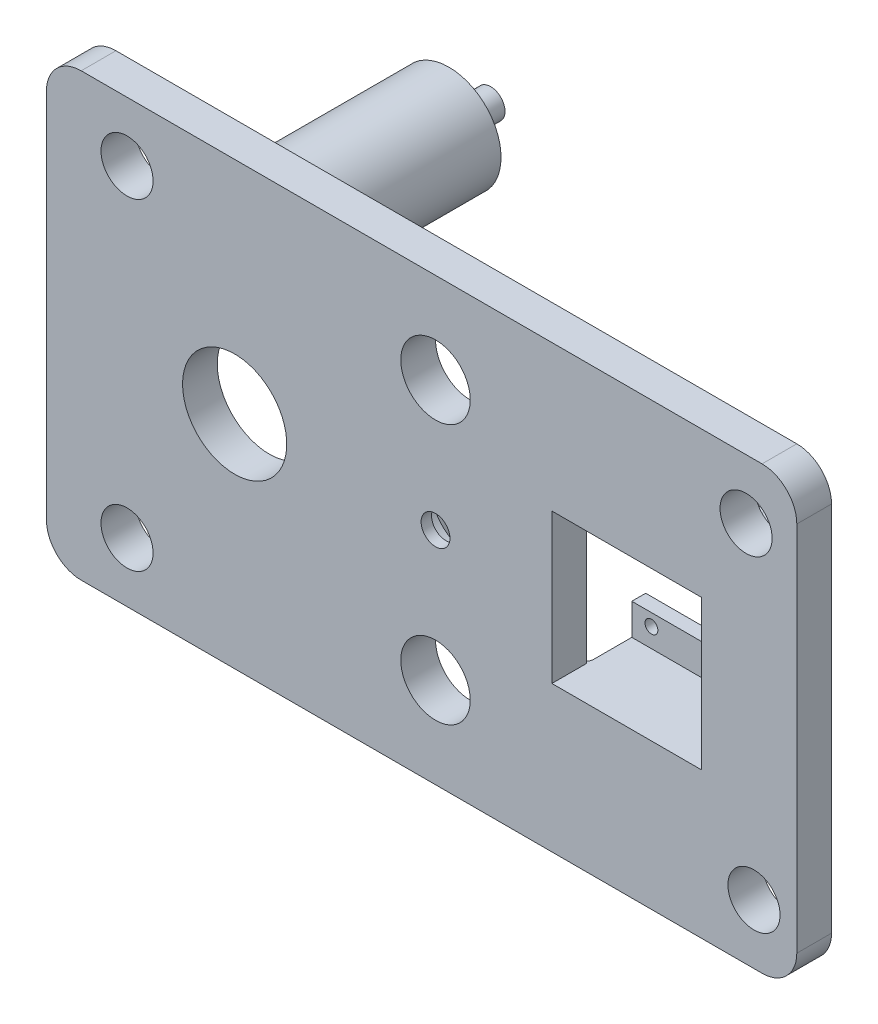
SolidWorks part; units mm, degrees
ref_plane "Front Plane" through (0, 0, 0) normal (0, 0, 1) x (1, 0, 0)
ref_plane "Top Plane" through (0, 0, 0) normal (0, 1, 0) x (1, 0, 0)
ref_plane "Right Plane" through (0, 0, 0) normal (1, 0, 0) x (0, 0, -1)
sketch "Sketch1" plane through (0, 0, 0) normal (0, 0, 1) x (1, 0, 0)
  line L1 (-108, 63.5) -> (108, 63.5)
  line L2 (-108, 63.5) -> (-108, -63.5)
  line L3 (-108, -63.5) -> (108, -63.5)
  line L4 (108, 63.5) -> (108, -63.5)
  line L5 (-108, 63.5) -> (108, -63.5) construction
  line L6 (-108, -63.5) -> (108, 63.5) construction
  point P0 (0, 0)
  dimension "D1" = 127
  dimension "D2" = 216
extrude "Boss-Extrude1" add sketch "Sketch1" along normal blind 10
fillet "Fillet1" radius 10 1 edges at (-108, 63.5, 5)
fillet "Fillet2" radius 10 3 edges at (-108, -63.5, 5) (108, 63.5, 5) (108, -63.5, 5)
sketch "Sketch9" plane through (0, 0, 0) normal (0, 0, -1) x (-1, 0, 0)
  line L0 (-98, 63.5) -> (98, 63.5) construction
  line L1 (-37.5, -21.5) -> (-80.5, -21.5)
  line L2 (-37.5, -21.5) -> (-37.5, 21.5)
  line L3 (-37.5, 21.5) -> (-80.5, 21.5)
  line L4 (-80.5, -21.5) -> (-80.5, 21.5)
  line L5 (-37.5, -21.5) -> (-80.5, 21.5) construction
  line L6 (-37.5, 21.5) -> (-80.5, -21.5) construction
  line L8 (108, 0) -> (-108, 0) construction
  line L9 (108, 53.5) -> (108, -53.5) construction
  line L10 (-108, -53.5) -> (-108, 53.5) construction
  circle A0 centre (-4, 0) radius 11.35
  point P2 (-59, 0)
  dimension "D6" = 22.7
  dimension "D1" = 27.5
  dimension "D2" = 55
  dimension "D3" = 43
  dimension "D4" = 43
  dimension "D5" = 63.5
extrude "Cut-Extrude4" cut sketch "Sketch9" against normal blind 7 contours A0
sketch "Sketch12" plane through (0, 0, 7) normal (0, 0, -1) x (-1, 0, 0)
  circle A0 centre (-4, 0) radius 4.15
  dimension "D1" = 8.3
extrude "Cut-Extrude5" cut sketch "Sketch12" against normal blind 7
extrude "Cut-Extrude6" cut sketch "Sketch9<4>" against normal through all contours L3 L4 L1 L2
sketch "Sketch9<4>" plane through (0, 0, 0) normal (0, 0, -1) x (-1, 0, 0) same geometry as "Sketch9"
sketch "Sketch13" plane through (0, 0, 0) normal (0, 0, -1) x (-1, 0, 0)
  line L1 (-37.5, -21.5) -> (-80.5, -21.5)
  line L2 (-37.5, -21.5) -> (-37.5, -25.5)
  line L3 (-37.5, -25.5) -> (-80.5, -25.5)
  line L4 (-80.5, -21.5) -> (-80.5, -25.5)
  dimension "D1" = 4
  dimension "D2" = 43
extrude "Boss-Extrude2" add sketch "Sketch13" along normal blind 17
ref_plane "Plane3" through (0, -21.5, 0) normal (0, 1, 0) x (1, 0, 0)
ref_plane "Plane4" through (0, 0, 0) normal (0, 0, -1) x (-1, 0, 0)
ref_plane "Plane6" through (80.5, 0, 0) normal (1, 0, 0) x (0, 0, -1)
sketch "Sketch16" plane through (80.5, 0, 0) normal (1, 0, 0) x (0, 0, -1)
  line L0 (17, -21.5) -> (0, -21.5) construction
  line L1 (17.0075, -21.5) -> (0.1109, -21.5)
  line L2 (17.0075, -21.5) -> (17.0075, -25.5)
  line L3 (17.0075, -25.5) -> (0.1109, -25.5)
  line L4 (0.1109, -21.5) -> (0.1109, -25.5)
  line L5 (17, -25.5) -> (0, -25.5) construction
fillet "Fillet4" radius 2 3 edges at (59, -25.5, 0) (37.5, -23.5, 0) (80.5, -23.5, 0)
sketch "Sketch17" plane through (0, -21.5, 0) normal (0, 1, 0) x (1, 0, 0)
  line L0 (80.5, 17.0075) -> (80.5, 0.1109) construction
  line L1 (37.5, 17) -> (80.5, 17)
  line L2 (37.5, 17) -> (37.5, 13)
  line L3 (37.5, 13) -> (80.5, 13)
  line L4 (80.5, 17) -> (80.5, 13)
  dimension "D1" = 4
extrude "Boss-Extrude5" add sketch "Sketch17" along normal blind 9
sketch "Sketch18" plane through (0, 0, 0) normal (0, 0, -1) x (-1, 0, 0)
  line L1 (-37.5, 21.5) -> (-80.5, 21.5)
  line L2 (-37.5, 21.5) -> (-37.5, 25.5)
  line L3 (-37.5, 25.5) -> (-80.5, 25.5)
  line L4 (-80.5, 21.5) -> (-80.5, 25.5)
  dimension "D1" = 43
  dimension "D2" = 4
extrude "Boss-Extrude6" add sketch "Sketch18" along normal blind 17
ref_plane "Plane7" through (0, 21.5, 0) normal (0, -1, 0) x (-1, 0, 0)
sketch "Sketch19" plane through (0, 21.5, 0) normal (0, -1, 0) x (-1, 0, 0)
  line L0 (-80.5, 17) -> (-80.5, 0) construction
  line L1 (-37.5, 17) -> (-80.5, 17)
  line L2 (-37.5, 17) -> (-37.5, 13)
  line L3 (-37.5, 13) -> (-80.5, 13)
  line L4 (-80.5, 17) -> (-80.5, 13)
  dimension "D1" = 4
extrude "Boss-Extrude7" add sketch "Sketch19" along normal blind 9
fillet "Fillet5" radius 2 3 edges at (37.5, 23.5, 0) (80.5, 23.5, 0) (59, 25.5, 0)
ref_plane "Plane8" through (0, 0, -17) normal (0, 0, -1) x (-1, 0, 0)
sketch "Sketch20" plane through (0, 0, -17) normal (0, 0, -1) x (-1, 0, 0)
  line L0 (-37.5, -25.5) -> (-37.5, -12.5) construction
  line L2 (-80.5, -21.5) -> (-37.5, -21.5)
  line L3 (-80.5, -12.5) -> (-80.5, -25.5) construction
  line L4 (-80.5, -12.5) -> (-37.5, -12.5) construction
  circle A0 centre (-43.15, -16) radius 1.85
  circle A1 centre (-74.85, -16) radius 1.85
  dimension "D3" = 5.5
  dimension "D4" = 3.7
  dimension "D5" = 5.65
  dimension "D6" = 3.7
  dimension "D1" = 5.65
  dimension "D2" = 9
extrude "Cut-Extrude7" cut sketch "Sketch20" against normal blind 9 contours A1 | A0
ref_plane "Plane9" through (0, 0, -17) normal (0, 0, -1) x (-1, 0, 0)
sketch "Sketch23" plane through (0, 0, -17) normal (0, 0, -1) x (-1, 0, 0)
  line L0 (-37.5, 21.5) -> (-80.5, 21.5)
  line L1 (-37.5, 12.5) -> (-37.5, 25.5) construction
  line L2 (-80.5, 25.5) -> (-80.5, 12.5) construction
  line L3 (-37.5, 12.5) -> (-80.5, 12.5) construction
  circle A0 centre (-43.15, 15.85) radius 1.85
  circle A1 centre (-74.85, 16) radius 1.85
  dimension "D4" = 3.7
  dimension "D5" = 3.7
  dimension "D6" = 5.65
  dimension "D7" = 5.65
  dimension "D1" = 9
  dimension "D2" = 5.5
  dimension "D3" = 5.65
extrude "Cut-Extrude8" cut sketch "Sketch23" against normal blind 9 contours A0 | A1
ref_plane "Plane10" through (0, 0, 0) normal (0, 0, -1) x (-1, 0, 0)
sketch "Sketch25" plane through (0, 0, 0) normal (0, 0, -1) x (-1, 0, 0)
  line L0 (5.8491, 5.5555) -> (-13.8858, -5.5762)
  line L1 (-4, -11.35) -> (-4, 11.35)
  line L2 (98, -63.5) -> (-98, -63.5) construction
  line L3 (-98, 63.5) -> (98, 63.5) construction
  circle A0 centre (5.8491, 5.5555) radius 0.0422
  circle A1 centre (-4, 0) radius 11.35 construction
  circle A2 centre (50.9816, -43.5) radius 15
  circle A3 centre (50.9816, 43.5) radius 15
  point P8 (-4.0184, -0.0104)
  dimension "D4" = 20
  dimension "D5" = 30
  dimension "D6" = 30
  dimension "D1" = 55
  dimension "D2" = 55
  dimension "D3" = 20
extrude "Boss-Extrude9" add sketch "Sketch25" along normal blind 48.84 contours A3 | A2
ref_plane "Plane11" through (0, 0, -48.84) normal (0, 0, -1) x (-1, 0, 0)
sketch "Sketch26" plane through (0, 0, -48.84) normal (0, 0, -1) x (-1, 0, 0)
  circle A0 centre (50.9816, -43.5) radius 4.15
  dimension "D1" = 8.3
extrude "Boss-Extrude10" add sketch "Sketch26" along normal blind 12
ref_plane "Plane12" through (0, 0, -48.84) normal (0, 0, -1) x (-1, 0, 0)
sketch "Sketch27" plane through (0, 0, -48.84) normal (0, 0, -1) x (-1, 0, 0)
  circle A0 centre (50.9816, 43.5) radius 4.15
  dimension "D1" = 8.3
extrude "Boss-Extrude11" add sketch "Sketch27" along normal blind 12
fillet "Fillet9" radius 2 1 edges at (-35.9816, -43.5, 0)
fillet "Fillet10" radius 2 1 edges at (-35.9816, 43.5, 0)
ref_plane "Plane13" through (0, 0, 10) normal (0, 0, 1) x (1, 0, 0)
sketch "Sketch28" plane through (0, 0, 10) normal (0, 0, 1) x (1, 0, 0)
  line L0 (98, 63.5) -> (-98, 63.5) construction
  line L3 (-98, -63.5) -> (98, -63.5) construction
  circle A0 centre (-84.8117, 46.37) radius 7.5
  circle A1 centre (-84.8117, -46.37) radius 7.5
  circle A2 centre (95.674, -46.3698) radius 7.5
  circle A3 centre (93.3991, 46.37) radius 7.5
  dimension "D2" = 15
  dimension "D3" = 17.13
  dimension "D4" = 15
  dimension "D5" = 17.13
  dimension "D6" = 15
  dimension "D7" = 15
  dimension "D1" = 17.13
extrude "Cut-Extrude9" cut sketch "Sketch28" against normal through all
ref_plane "Plane14" through (0, 0, 0) normal (0, 0, -1) x (-1, 0, 0)
sketch "Sketch29" plane through (0, 0, 0) normal (0, 0, -1) x (-1, 0, 0)
  line L0 (-108, 0) -> (108, 0) construction
  line L1 (-108, -53.5) -> (-108, 53.5) construction
  line L2 (108, 53.5) -> (108, -53.5) construction
  line L3 (-4, -11.35) -> (-4, -63.5) construction
  line L5 (98, -63.5) -> (-98, -63.5) construction
  line L7 (-4, 11.35) -> (-4, 63.5) construction
  line L8 (-98, 63.5) -> (98, 63.5) construction
  circle A5 centre (-4, 0) radius 11.35 construction
  circle A6 centre (-4, 0) radius 11.35 construction
  circle A7 centre (-4, 37.425) radius 10
  circle A8 centre (53.8283, 0) radius 15
  circle A9 centre (-4, -37.425) radius 10
  dimension "D1" = 20
  dimension "D2" = 30
extrude "Cut-Extrude10" cut sketch "Sketch29" against normal through all contours A8 | A9 | A7 region at (-53.8283, 0, 0) region at (4, -37.425, 0)
